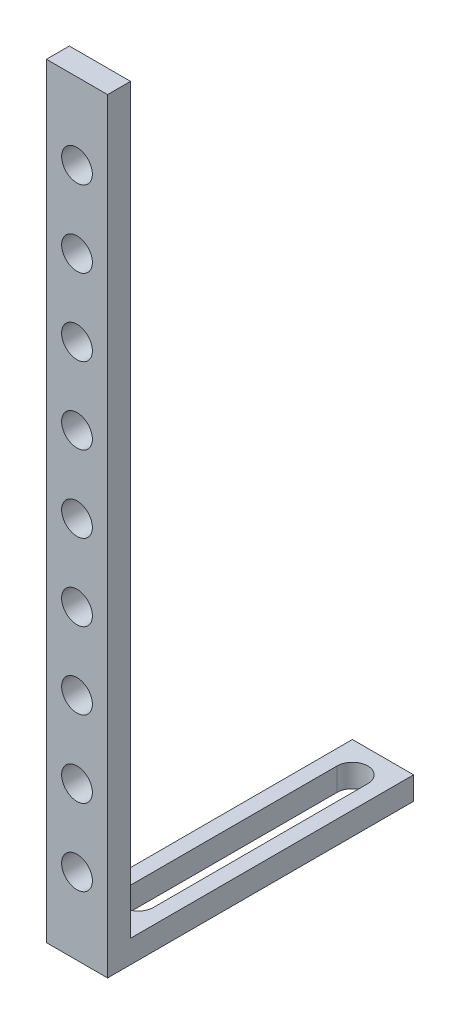
SolidWorks part; units mm, degrees
ref_plane "Спереди" through (0, 0, 0) normal (0, 0, 1) x (1, 0, 0)
ref_plane "Сверху" through (0, 0, 0) normal (0, 1, 0) x (1, 0, 0)
ref_plane "Справа" through (0, 0, 0) normal (1, 0, 0) x (0, 0, -1)
sketch "Эскиз1" plane through (0, 0, 0) normal (1, 0, 0) x (0, 0, -1)
  line L0 (0, 0) -> (0, 500)
  line L1 (0, 500) -> (15, 500)
  line L2 (15, 500) -> (15, 15)
  line L3 (15, 15) -> (200, 15)
  line L4 (200, 15) -> (200, 0)
  line L5 (200, 0) -> (0, 0)
extrude "Бобышка-Вытянуть1" add sketch "Эскиз1" along normal blind 40
sketch "Эскиз2" plane through (0, 0, 0) normal (0, 0, 1) x (1, 0, 0)
  circle A0 centre (20, 50) radius 10.05
  circle A1 centre (20, 100) radius 10.05
  circle A2 centre (20, 150) radius 10.05
  circle A3 centre (20, 200) radius 10.05
  circle A4 centre (20, 250) radius 10.05
  circle A5 centre (20, 300) radius 10.05
  circle A6 centre (20, 350) radius 10.05
  circle A7 centre (20, 400) radius 10.05
  circle A8 centre (20, 450) radius 10.05
  dimension "D1" = 9
extrude "Вырез-Вытянуть1" cut sketch "Эскиз2" against normal through all
sketch "Эскиз3" plane through (0, 0, 0) normal (0, -1, 0) x (1, 0, 0)
  line L0 (9.95, -40) -> (9.95, -180)
  line L1 (30.05, -40) -> (30.05, -180)
  arc A0 (9.95, -40) -> (30.05, -40) centre (20, -40) cw
  arc A1 (9.95, -180) -> (30.05, -180) centre (20, -180) ccw
  point P6 (0, 0)
  point P7 (0, 0)
extrude "Вырез-Вытянуть2" cut sketch "Эскиз3" against normal up to next
